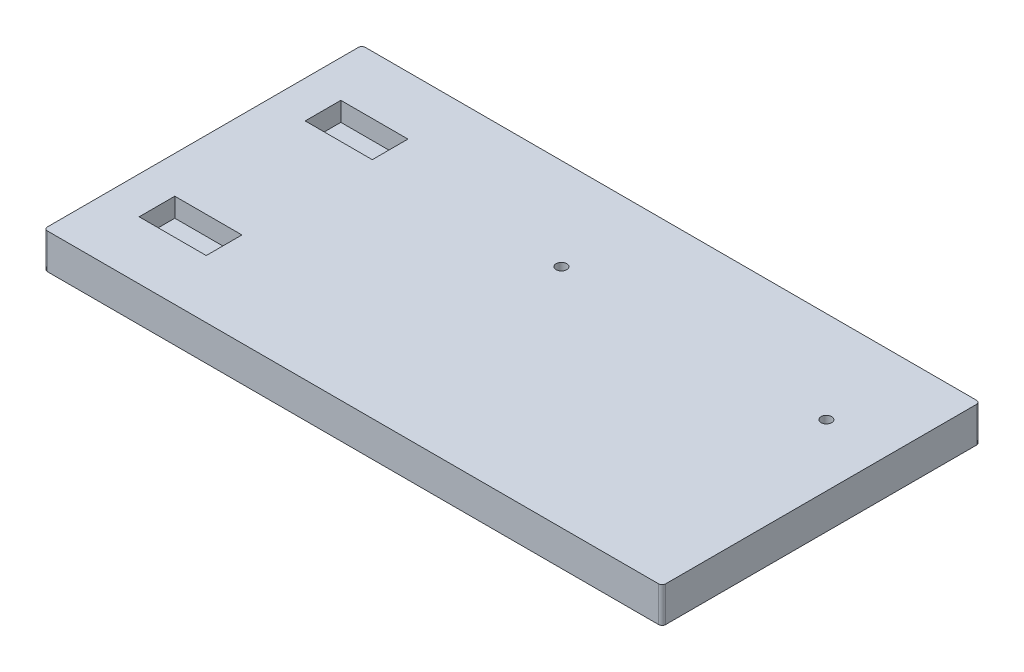
SolidWorks part; units mm, degrees
ref_plane "Front Plane" through (0, 0, 0) normal (0, 0, 1) x (1, 0, 0)
ref_plane "Top Plane" through (0, 0, 0) normal (0, 1, 0) x (1, 0, 0)
ref_plane "Right Plane" through (0, 0, 0) normal (1, 0, 0) x (0, 0, -1)
sketch "Sketch1" plane through (0, 0, 0) normal (0, 1, 0) x (1, 0, 0)
  line L1 (87.5, -45) -> (-87.5, -45)
  line L2 (87.5, -45) -> (87.5, 45)
  line L3 (87.5, 45) -> (-87.5, 45)
  line L4 (-87.5, -45) -> (-87.5, 45)
  line L5 (87.5, -45) -> (-87.5, 45) construction
  line L6 (87.5, 45) -> (-87.5, -45) construction
  point P0 (0, 0)
  dimension "D1" = 175
  dimension "D2" = 90
extrude "Boss-Extrude1" add sketch "Sketch1" along normal blind 10
sketch "Sketch2" plane through (0, 10, 0) normal (0, 1, 0) x (1, 0, 0)
  line L0 (-87.5, 45) -> (-87.5, -45) construction
  line L5 (-67.5, -23.5) -> (-67.5, 0) construction
  line L6 (-77, -28.55) -> (-58, -28.55)
  line L7 (0, 0) -> (-87.5, 0) construction
  line L8 (-77, -28.55) -> (-77, -18.45)
  line L9 (-77, -18.45) -> (-58, -18.45)
  line L10 (-58, -28.55) -> (-58, -18.45)
  line L11 (-77, -28.55) -> (-58, -18.45) construction
  line L12 (-77, -18.45) -> (-58, -28.55) construction
  circle A0 centre (-5, 19) radius 1.5
  circle A1 centre (70, 19) radius 1.5
  point P0 (-67.5, -23.5)
  dimension "D6" = 19
  dimension "D8" = 3
  dimension "D1" = 19
  dimension "D2" = 10.1
  dimension "D3" = 23.5
  dimension "D4" = 20
  dimension "D5" = 62.5
  dimension "D7" = 75
extrude "Cut-Extrude1" cut sketch "Sketch2" against normal blind 5.4 contours L6 L10 L9 L8 region at (-67.5, 10, 23.5)
mirror "Mirror1" about plane through (0, 0, 0) normal (0, 0, 1) of "Cut-Extrude1"
extrude "Cut-Extrude3" cut sketch "Sketch2<8>" against normal through all contours A0 | A1
sketch "Sketch2<8>" plane through (0, 10, 0) normal (0, 1, 0) x (1, 0, 0) same geometry as "Sketch2"
fillet "Fillet1" radius 1 4 edges at (-87.5, 5, -45) (87.5, 5, -45) (87.5, 5, 45) (-87.5, 5, 45)
